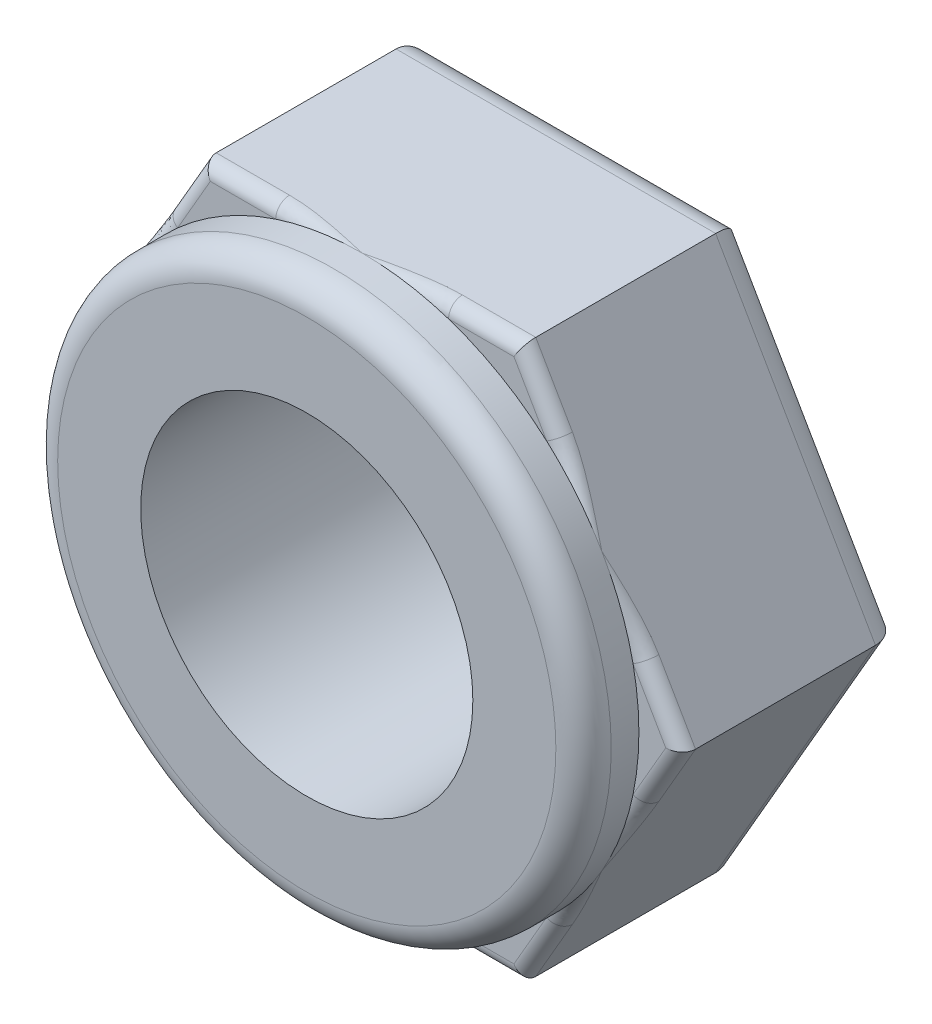
SolidWorks part; units mm, degrees
ref_plane "前视基准面" through (0, 0, 0) normal (0, 0, 1) x (1, 0, 0)
ref_plane "上视基准面" through (0, 0, 0) normal (0, 1, 0) x (1, 0, 0)
ref_plane "右视基准面" through (0, 0, 0) normal (1, 0, 0) x (0, 0, -1)
sketch "草图1" plane through (0, 0, 0) normal (0, 0, 1) x (1, 0, 0)
  line L1 (11.547, 0) -> (5.7735, 10)
  line L2 (5.7735, 10) -> (-5.7735, 10)
  line L3 (-5.7735, 10) -> (-11.547, 0)
  line L4 (-11.547, 0) -> (-5.7735, -10)
  line L5 (-5.7735, -10) -> (5.7735, -10)
  line L6 (5.7735, -10) -> (11.547, 0)
  circle A0 centre (0, 0) radius 10 construction
  circle A1 centre (0, 0) radius 6
  dimension "D2" = 12
  dimension "D1" = 20
extrude "拉伸1" add sketch "草图1" along normal blind 8
sketch "草图2" plane through (0, 0, 8) normal (0, 0, 1) x (1, 0, 0)
  circle A0 centre (0, 0) radius 6
  circle A1 centre (0, 0) radius 10
extrude "拉伸2" add sketch "草图2" along normal blind 2
fillet "圆角1" radius 1 1 edges at (10, 0, 10)
fillet "圆角2" radius 1 6 edges at (8.6603, -5, 0) (0, -10, 0) (-8.6603, -5, 0) (0, 10, 0) (-8.6603, 5, 0) (8.6603, 5, 0)
fillet "圆角3" radius 0.5 12 edges at (-10.1036, -2.5, 8) (-7.2169, 7.5, 8) (-2.8868, -10, 8) (10.1036, -2.5, 8) (2.8868, 10, 8) (10.1036, 2.5, 8) (-7.2169, -7.5, 8) (-10.1036, 2.5, 8) (2.8868, -10, 8) (7.2169, -7.5, 8) (-2.8868, 10, 8) (7.2169, 7.5, 8)
